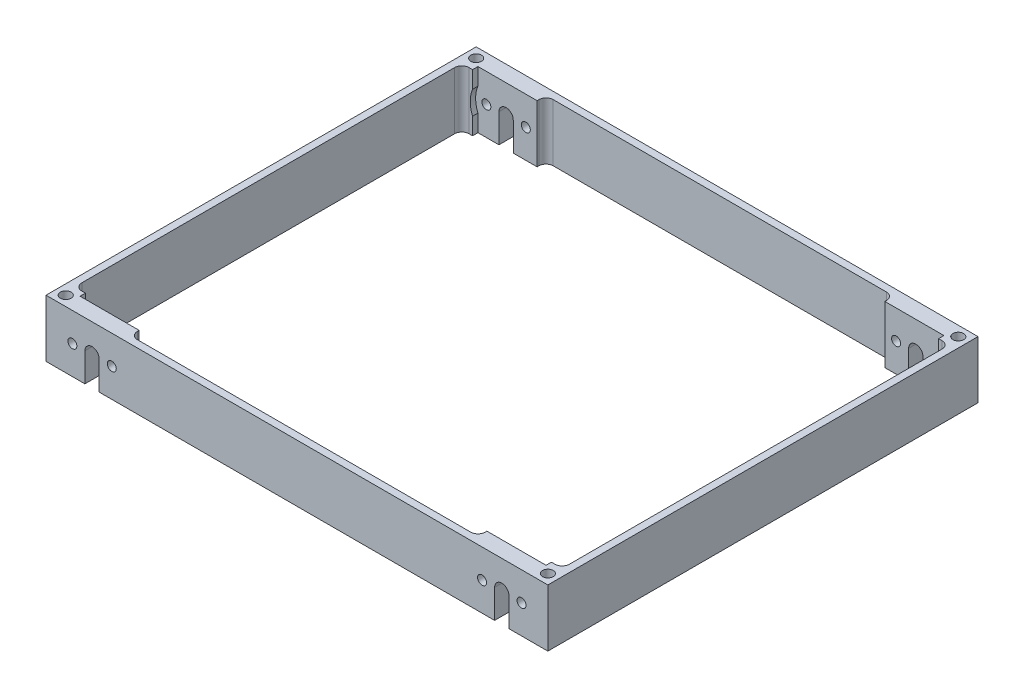
SolidWorks part; units mm, degrees
ref_plane "Front Plane" through (0, 0, 0) normal (0, 0, 1) x (1, 0, 0)
ref_plane "Top Plane" through (0, 0, 0) normal (0, 1, 0) x (1, 0, 0)
ref_plane "Right Plane" through (0, 0, 0) normal (1, 0, 0) x (0, 0, -1)
sketch "Sketch1" plane through (0, 0, 0) normal (0, 1, 0) x (1, 0, 0)
  line L0 (-135.5, 115.5) -> (-4.5, 115.5)
  line L1 (-140, 120) -> (0, 120)
  line L2 (-140, 120) -> (-140, 0)
  line L3 (-140, 0) -> (0, 0)
  line L4 (0, 120) -> (0, 0)
  line L5 (-4.5, 115.5) -> (-4.5, 4.5)
  line L6 (-135.5, 4.5) -> (-4.5, 4.5)
  line L7 (-135.5, 115.5) -> (-135.5, 4.5)
  dimension "D1" = 120
  dimension "D2" = 140
  dimension "D3" = 4.5
extrude "Boss-Extrude1" add sketch "Sketch1" along normal blind 16
sketch "Sketch3" plane through (0, 0, 0) normal (0, 0, 1) x (1, 0, 0)
  line L0 (-140, 8) -> (-129.15, 8) construction
  line L1 (-140, 16) -> (-140, 0) construction
  line L2 (0, 16) -> (0, 0) construction
  line L3 (-10.85, 8) -> (0, 8) construction
  line L4 (-127.15, 8) -> (-12.85, 8) construction
  line L5 (-129.15, 8) -> (-129.15, 0)
  line L6 (-140, 0) -> (0, 0) construction
  line L7 (-125.15, 8) -> (-125.15, 0)
  line L8 (-14.85, 8) -> (-14.85, 0)
  line L9 (-10.85, 8) -> (-10.85, 0)
  line L10 (-10.85, 0) -> (-14.85, 0)
  line L11 (-129.15, 0) -> (-125.15, 0)
  arc A0 (-125.15, 8) -> (-129.15, 8) centre (-127.15, 8) ccw
  arc A1 (-10.85, 8) -> (-14.85, 8) centre (-12.85, 8) ccw
  dimension "D1" = 4
  dimension "D2" = 114.3
extrude "Cut-Extrude1" cut sketch "Sketch3" against normal through all
sketch "Sketch5" plane through (0, 0, 0) normal (0, 0, 1) x (1, 0, 0)
  line L0 (-127.15, 8) -> (-132.65, 8) construction
  line L1 (-127.15, 8) -> (-121.65, 8) construction
  line L2 (-70, 16) -> (-70, 0) construction
  line L3 (-140, 16) -> (0, 16) construction
  line L4 (-125.15, 0) -> (-14.85, 0) construction
  circle A0 centre (-132.65, 8) radius 1.25
  circle A1 centre (-121.65, 8) radius 1.25
  circle A2 centre (-18.35, 8) radius 1.25
  circle A3 centre (-7.35, 8) radius 1.25
  dimension "D2" = 2.5
  dimension "D1" = 11
extrude "Cut-Extrude3" cut sketch "Sketch5" against normal through all
sketch "Sketch4" plane through (0, 16, 0) normal (0, 1, 0) x (1, 0, 0)
  line L1 (-138, 115.5) -> (-118.5, 115.5)
  line L2 (-138, 115.5) -> (-138, 4.5)
  line L3 (-138, 4.5) -> (-118.5, 4.5)
  line L4 (-2, 115.5) -> (-2, 4.5)
  line L5 (-135.5, 4.5) -> (-4.5, 4.5) construction
  line L6 (-4.5, 115.5) -> (-135.5, 115.5) construction
  line L7 (-140, 120) -> (-140, 0) construction
  line L8 (0, 0) -> (0, 120) construction
  line L9 (-118.5, 4.5) -> (-118.5, 2)
  line L10 (-118.5, 118) -> (-21.5, 118)
  line L11 (-118.5, 118) -> (-118.5, 115.5)
  line L12 (-118.5, 2) -> (-21.5, 2)
  line L13 (-21.5, 118) -> (-21.5, 115.5)
  line L14 (-21.5, 115.5) -> (-2, 115.5)
  line L15 (-21.5, 4.5) -> (-2, 4.5)
  line L16 (-21.5, 4.5) -> (-21.5, 2)
  line L19 (-70, 118) -> (-70, 2) construction
  dimension "D1" = 2
  dimension "D2" = 2
  dimension "D3" = 2.5
  dimension "D4" = 19.5
extrude "Cut-Extrude2" cut sketch "Sketch4" against normal through all
sketch "Sketch6" plane through (0, 0, 0) normal (0, 0, 1) x (1, 0, 0)
  line L0 (-138, 16) -> (-138, 0) construction
  line L1 (-140, 16) -> (0, 16) construction
  line L2 (-140, 0) -> (-129.15, 0) construction
  line L3 (-140, 16) -> (-140, 0) construction
  line L7 (-140, 16) -> (-135, 16)
  line L8 (-140, 8) -> (0, 8) construction
  line L9 (0, 16) -> (0, 0) construction
  line L10 (-70, 16) -> (-70, 0) construction
  line L11 (-125.15, 0) -> (-14.85, 0) construction
  line L24 (-140, 16) -> (-140, 0)
  line L25 (-135, 16) -> (-135, 11.26)
  line L26 (-135, 0) -> (-140, 0)
  line L27 (-5, 16) -> (-5, 11.26)
  line L28 (0, 16) -> (-5, 16)
  line L29 (0, 16) -> (0, 0)
  line L30 (-5, 0) -> (0, 0)
  line L31 (-135, 4.74) -> (-135, 0)
  line L32 (-5, 4.74) -> (-5, 0)
  arc A1 (-135, 11.26) -> (-135, 4.74) centre (-127.15, 8) ccw
  arc A2 (-5, 11.26) -> (-5, 4.74) centre (-12.85, 8) cw
  dimension "D1" = 2
  dimension "D2" = 5
extrude "Boss-Extrude2" add sketch "Sketch6" against normal up to surface (115.5 mm away) up to face at (-127.7, 6.25, -115.5)
sketch "Sketch7" plane through (0, 16, 0) normal (0, 1, 0) x (1, 0, 0)
  line L0 (-140, 120) -> (-140, 0) construction
  line L1 (-138, 114) -> (-2, 114)
  line L2 (-138, 114) -> (-138, 6)
  line L3 (-138, 6) -> (-2, 6)
  line L4 (-2, 114) -> (-2, 6)
  line L5 (0, 0) -> (0, 120) construction
  line L6 (0, 120) -> (-140, 120) construction
  line L7 (-140, 0) -> (0, 0) construction
  dimension "D1" = 2
  dimension "D2" = 2
  dimension "D3" = 6
  dimension "D4" = 6
extrude "Cut-Extrude4" cut sketch "Sketch7" against normal through all contours L2 L1 L4 L3
fillet "Fillet1" radius 2 8 edges at (-21.5, 8, -2) (-118.5, 8, -2) (-21.5, 8, -118) (-118.5, 8, -118) (-2, 8, -6) (-138, 8, -6) (-2, 8, -114) (-138, 8, -114)
ref_plane "Plane1" through (-118.5, 16, -4.5) normal (1, 0, 0) x (0, 0, -1)
sketch "Sketch9" plane through (0, 0, 0) normal (0, 1, 0) x (1, 0, 0)
  line L0 (-70, 120) -> (-70, 0) construction
  line L1 (0, 120) -> (-140, 120) construction
  line L2 (-140, 0) -> (0, 0) construction
  line L4 (-140, 120) -> (-140, 0) construction
  line L5 (-140, 60) -> (0, 60) construction
  line L6 (0, 0) -> (0, 120) construction
  circle A0 centre (-137.25, 2.75) radius 1.5
  circle A1 centre (-2.75, 2.75) radius 1.5
  circle A2 centre (-2.75, 117.25) radius 1.5
  circle A3 centre (-137.25, 117.25) radius 1.5
  dimension "D1" = 2.75
  dimension "D2" = 3
  dimension "D3" = 2.75
extrude "Cut-Extrude5" cut sketch "Sketch9" along normal blind 4
sketch "Sketch10" plane through (0, 16, 0) normal (0, 1, 0) x (1, 0, 0)
  line L0 (-70, 120) -> (-70, 0) construction
  line L1 (0, 120) -> (-140, 120) construction
  line L2 (-140, 0) -> (0, 0) construction
  line L3 (-137.25, 117.25) -> (-137.25, 120) construction
  line L4 (-140, 120) -> (-140, 0) construction
  line L5 (-140, 60) -> (0, 60) construction
  line L6 (0, 0) -> (0, 120) construction
  line L7 (-137.25, 117.25) -> (-140, 117.25) construction
  circle A0 centre (-137.25, 117.25) radius 1.5
  circle A1 centre (-2.75, 117.25) radius 1.5
  circle A2 centre (-2.75, 2.75) radius 1.5
  circle A3 centre (-137.25, 2.75) radius 1.5
  dimension "D1" = 3
  dimension "D2" = 2.75
extrude "Cut-Extrude6" cut sketch "Sketch10" against normal through all
